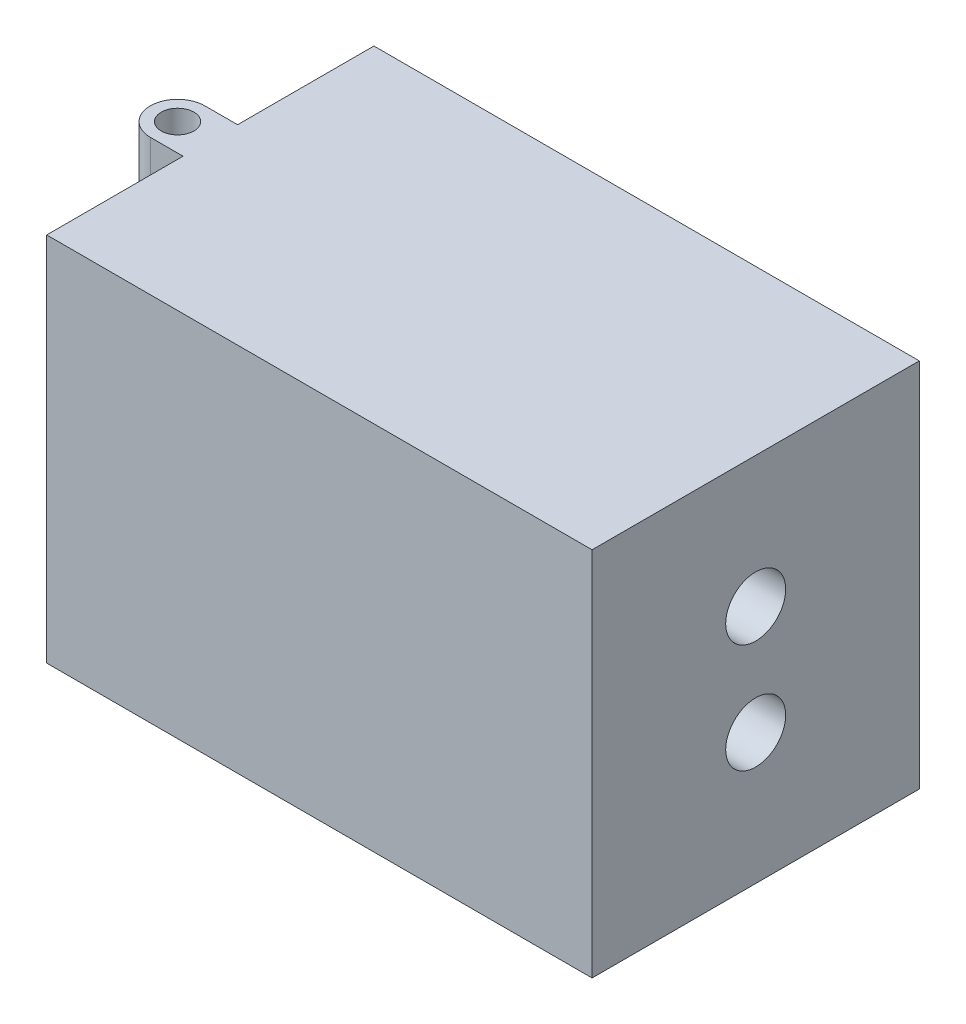
SolidWorks part; units mm, degrees
ref_plane "Plan de face" through (0, 0, 0) normal (0, 0, 1) x (1, 0, 0)
ref_plane "Plan de dessus" through (0, 0, 0) normal (0, 1, 0) x (1, 0, 0)
ref_plane "Plan de droite" through (0, 0, 0) normal (1, 0, 0) x (0, 0, -1)
sketch "Esquisse1" plane through (0, 0, 0) normal (0, 0, 1) x (1, 0, 0)
  line L1 (0, 0) -> (50, 0)
  line L2 (0, 0) -> (0, 34)
  line L3 (0, 34) -> (50, 34)
  line L4 (50, 0) -> (50, 34)
  dimension "D1" = 34
  dimension "D2" = 50
extrude "Boss.-Extru.1" add sketch "Esquisse1" along normal blind 30
sketch "Esquisse10" plane through (0, 34, 0) normal (0, 1, 0) x (1, 0, 0)
  line L0 (0, 0) -> (0, -12.5) construction
  line L1 (0, -30) -> (0, 0) construction
  line L2 (0, -12.5) -> (0, -17.5)
  line L3 (0, -17.5) -> (0, -30) construction
  line L4 (0, -12.5) -> (-3, -12.5)
  line L5 (-3, -12.5) -> (-3, -17.5) construction
  line L6 (-3, -17.5) -> (0, -17.5)
  arc A1 (-3, -12.5) -> (-3, -17.5) centre (-3, -15) ccw
  circle A2 centre (-3, -15) radius 1.5
  dimension "D3" = 3
  dimension "D1" = 5
  dimension "D2" = 3
extrude "Boss.-Extru.3" add sketch "Esquisse10" against normal blind 5
ref_plane "Plan2" through (0, 17, 0) normal (0, 1, 0) x (1, 0, 0)
mirror "Symétrie2" about plane through (0, 17, 0) normal (0, 1, 0) of "Boss.-Extru.3"
sketch "Esquisse11" plane through (0, 0, 0) normal (-1, 0, 0) x (0, 0, 1)
  line L0 (12.5, 5) -> (12.5, 7) construction
  line L1 (17.5, 29) -> (17.5, 27) construction
  line L2 (17.5, 27) -> (12.5, 7) construction
  line L3 (15, 22) -> (15, 12) construction
  line L4 (30, 34) -> (17.5, 34) construction
  line L5 (10.3812, 12) -> (12.6906, 8)
  line L6 (12.6906, 8) -> (17.3094, 8)
  line L7 (17.3094, 8) -> (19.6188, 12)
  line L8 (19.6188, 12) -> (17.3094, 16)
  line L9 (17.3094, 16) -> (12.6906, 16)
  line L10 (12.6906, 16) -> (10.3812, 12)
  line L11 (10.3812, 22) -> (12.6906, 18)
  line L12 (12.6906, 18) -> (17.3094, 18)
  line L13 (17.3094, 18) -> (19.6188, 22)
  line L14 (19.6188, 22) -> (17.3094, 26)
  line L15 (17.3094, 26) -> (12.6906, 26)
  line L16 (12.6906, 26) -> (10.3812, 22)
  circle A0 centre (15, 12) radius 4 construction
  circle A1 centre (15, 22) radius 4 construction
  point P9 (15, 17)
  dimension "D1" = 2
  dimension "D2" = 2
  dimension "D3" = 5
  dimension "D4" = 8
extrude "Enlèv. mat.-Extru.6" cut sketch "Esquisse11" against normal blind 45
sketch "Esquisse12" plane through (0, 0, 0) normal (-1, 0, 0) x (0, 0, 1)
  line L0 (12.6906, 8) -> (17.3094, 16) construction
  line L1 (12.6906, 18) -> (17.3094, 26) construction
  circle A0 centre (15, 12) radius 2.75
  circle A1 centre (15, 22) radius 2.75
  dimension "D1" = 5.5
extrude "Enlèv. mat.-Extru.7" cut sketch "Esquisse12" against normal through all
